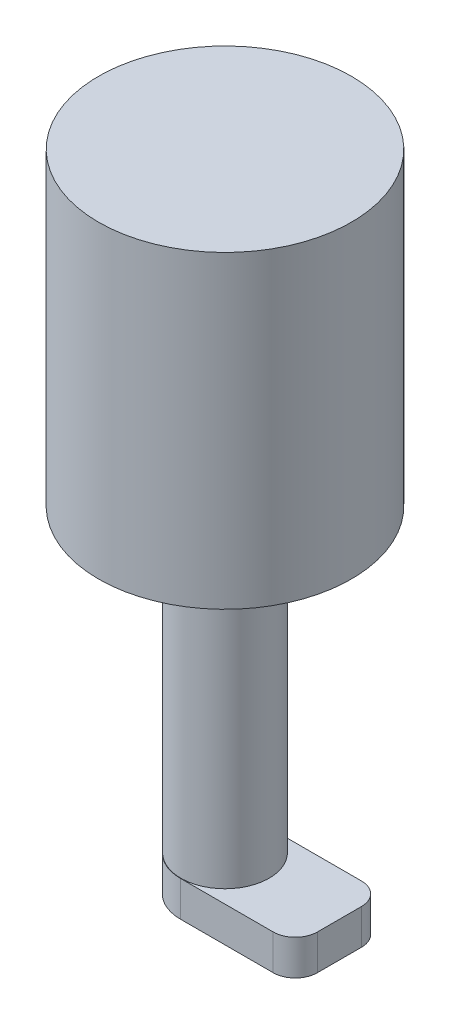
SolidWorks part; units mm, degrees
ref_plane "Front Plane" through (0, 0, 0) normal (0, 0, 1) x (1, 0, 0)
ref_plane "Top Plane" through (0, 0, 0) normal (0, 1, 0) x (1, 0, 0)
ref_plane "Right Plane" through (0, 0, 0) normal (1, 0, 0) x (0, 0, -1)
sketch "Sketch2" plane through (0, 0, 0) normal (0, 1, 0) x (1, 0, 0)
  circle A0 centre (0, 0) radius 28.64
extrude "Boss-Extrude1" add sketch "Sketch2" along normal blind 70
sketch "Sketch3" plane through (0, 0, 0) normal (0, -1, 0) x (1, 0, 0)
  circle A0 centre (0, 0) radius 10
  dimension "D1" = 20
extrude "Boss-Extrude2" add sketch "Sketch3" along normal blind 68
sketch "Sketch7" plane through (0, -68, 0) normal (0, -1, 0) x (1, 0, 0)
  line L0 (-10, 10.0775) -> (-10, -9.9225)
  line L1 (26, -9.9225) -> (-10, -9.9225)
  line L2 (26, -9.9225) -> (26, 10.0775)
  line L3 (26, 10.0775) -> (-10, 10.0775)
  line L5 (26, -9.9225) -> (-10, 3.8164) construction
  line L6 (26, 10.0775) -> (-10, -3.8759) construction
  circle A0 centre (0, 0) radius 10 construction
  point P0 (0, 0)
  dimension "D1" = 26
  dimension "D2" = 20
extrude "Boss-Extrude3" add sketch "Sketch7" along normal blind 8
fillet "Fillet1" radius 10 2 edges at (-10, -72, -9.9225) (-10, -72, 10.0775)
fillet "Fillet2" radius 5 2 edges at (26, -72, -9.9225) (26, -72, 10.0775)
